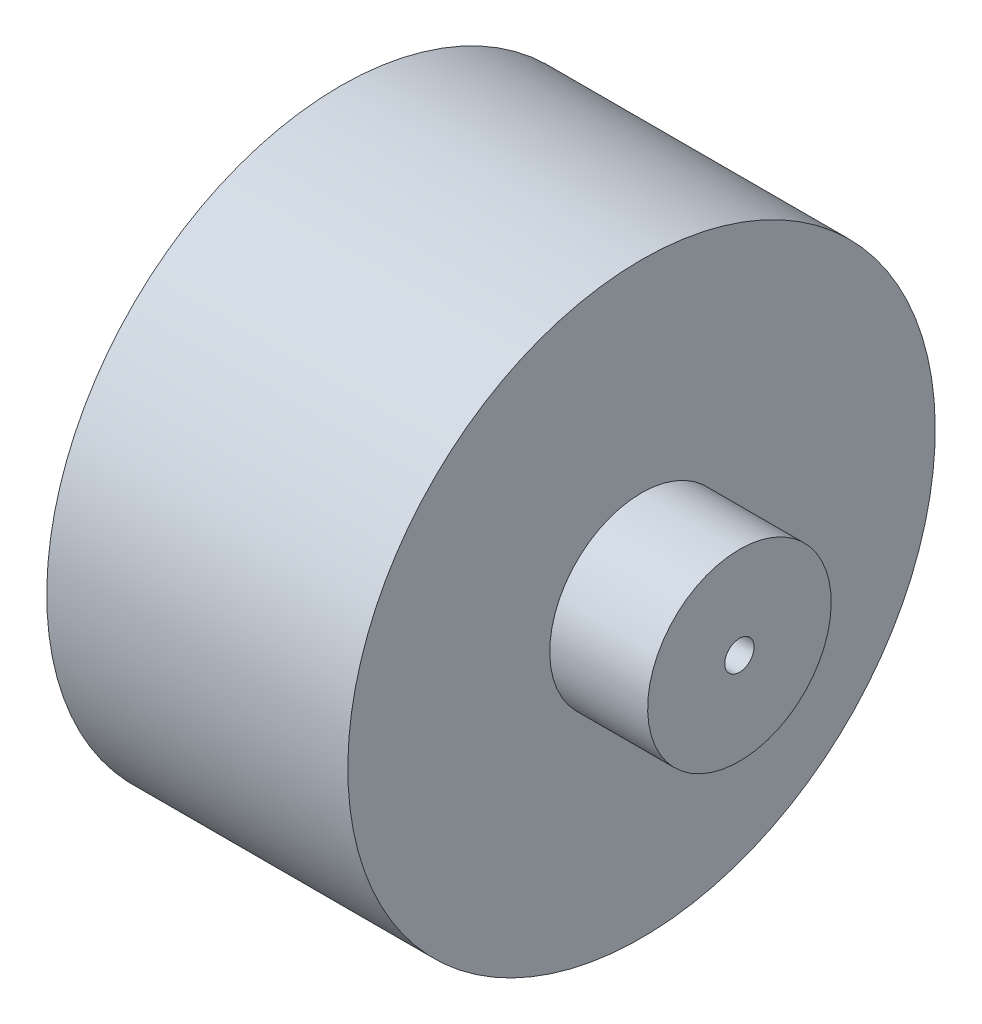
SolidWorks part; units mm, degrees
ref_plane "Front Plane" through (0, 0, 0) normal (0, 0, 1) x (1, 0, 0)
ref_plane "Top Plane" through (0, 0, 0) normal (0, 1, 0) x (1, 0, 0)
ref_plane "Right Plane" through (0, 0, 0) normal (1, 0, 0) x (0, 0, -1)
sketch "Sketch1" plane through (0, 0, 0) normal (0, 0, 1) x (1, 0, 0)
  line L0 (-25, 0) -> (-163, 0)
  line L1 (0, 0) -> (-40.8199, 0) construction
  line L2 (-163, 0) -> (-163, 120)
  line L3 (-163, 120) -> (-40, 120)
  line L4 (-40, 120) -> (-40, 37.5)
  line L5 (-40, 37.5) -> (0, 37.5)
  line L6 (-25, 0) -> (-25, 6)
  line L7 (-25, 6) -> (0, 6)
  line L8 (0, 6) -> (0, 37.5)
  point P8 (-0.5582, 15.0099)
  dimension "D1" = 12
  dimension "D2" = 240
  dimension "D3" = 123
  dimension "D4" = 40
  dimension "D5" = 25
  dimension "D6" = 75
revolve "Revolve1" add sketch "Sketch1" angle 360 about L1
